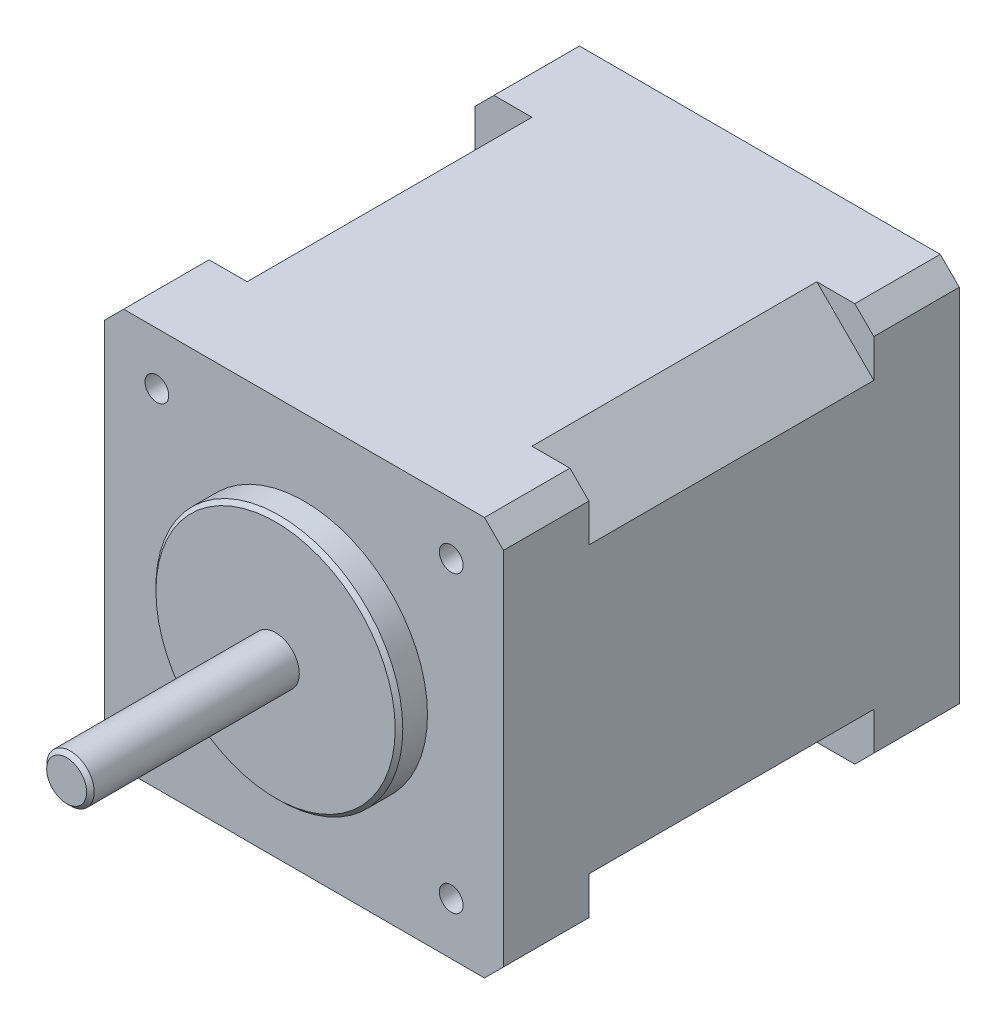
SolidWorks part; units mm, degrees
ref_plane "Plan de face" through (0, 0, 0) normal (0, 0, 1) x (1, 0, 0)
ref_plane "Plan de dessus" through (0, 0, 0) normal (0, 1, 0) x (1, 0, 0)
ref_plane "Plan de droite" through (0, 0, 0) normal (1, 0, 0) x (0, 0, -1)
sketch "Esquisse1" plane through (0, 0, 0) normal (0, 0, 1) x (1, 0, 0)
  line L1 (-21, 21) -> (21, 21)
  line L2 (-21, 21) -> (-21, -21)
  line L3 (-21, -21) -> (21, -21)
  line L4 (21, 21) -> (21, -21)
  dimension "D1" = 42
  dimension "D2" = 42
  dimension "D3" = 21
  dimension "D4" = 21
extrude "Boss.-Extru.1" add sketch "Esquisse1" along normal blind 48
chamfer "Chanfrein1" distance 2 angle 45 4 edges at (-21, -21, 24) (21, -21, 24) (-21, 21, 24) (21, 21, 24)
sketch "Esquisse3" plane through (0, 0, 48) normal (0, 0, 1) x (1, 0, 0)
  circle A0 centre (0, 0) radius 13
  dimension "D1" = 26
extrude "Boss.-Extru.2" add sketch "Esquisse3" along normal blind 3
hole_wizard "Trou pour taraudage pour trou taraudé M3x0.51" positions "Esquisse5" profile "Esquisse6" hole size "M3x0.5" standard "Ansi Metric" end condition through all
sketch "Esquisse5" plane through (0, 0, 48) normal (0, 0, 1) x (1, 0, 0)
  line L0 (19, 21) -> (-19, 21) construction
  line L1 (-19, -21) -> (19, -21) construction
  line L2 (-21, 19) -> (-21, -19) construction
  line L3 (21, -19) -> (21, 19) construction
  point P0 (-15.5, 15.5)
  point P2 (-15.5, -15.5)
  point P4 (15.5, -15.5)
  point P6 (15.5, 15.5)
  dimension "D1" = 5.5
  dimension "D2" = 5.5
  dimension "D3" = 5.5
  dimension "D4" = 5.5
  dimension "D5" = 5.5
  dimension "D6" = 5.5
  dimension "D7" = 5.5
  dimension "D8" = 5.5
sketch "Esquisse6" plane through (-15.5, 15.5, 48) normal (1, 0, 0) x (0, -1, 0)
  line L0 (0, 0) -> (0, 48)
  line L1 (0, 48) -> (1.25, 48)
  line L2 (1.25, 48) -> (1.25, 0)
  line L5 (1.25, 0) -> (0, 0)
  line L11 (0, -6.35) -> (0, 107.95) construction
  dimension "Diamètre du perçage jusqu'au prochain" = 2.5
  dimension "Profondeur du perçage jusqu'au prochain" = 48
sketch "Esquisse7" plane through (0, 0, 51) normal (0, 0, 1) x (1, 0, 0)
  circle A0 centre (0, 0) radius 2.5
  dimension "D1" = 5
extrude "Boss.-Extru.3" add sketch "Esquisse7" along normal blind 22
chamfer "Chanfrein2" distance 0.4 angle 45 1 edges at (2.5, 0, 73)
chamfer "Chanfrein3" distance 0.4 angle 45 1 edges at (13, 0, 51)
sketch "Esquisse9" plane through (0, 0, 0) normal (0, 0, -1) x (-1, 0, 0)
  line L0 (-21, 15) -> (-15, 21)
  line L1 (-21, -19) -> (-21, 19) construction
  line L2 (-19, 21) -> (19, 21) construction
  line L3 (-15, 21) -> (-21, 21)
  line L4 (-21, 21) -> (-21, 15)
  line L5 (15, 21) -> (21, 15)
  line L6 (21, 19) -> (21, -19) construction
  line L7 (21, 15) -> (21, 21)
  line L8 (21, 21) -> (15, 21)
  line L9 (-21, -15) -> (-15, -21)
  line L10 (19, -21) -> (-19, -21) construction
  line L11 (-15, -21) -> (-21, -21)
  line L12 (-21, -21) -> (-21, -15)
  line L13 (15, -21) -> (21, -15)
  line L14 (21, -15) -> (21, -21)
  line L15 (21, -21) -> (15, -21)
  dimension "D1" = 6
extrude "Enlèv. mat.-Extru.1" cut sketch "Esquisse9" against normal blind 30 from offset 9 offset against normal yes
